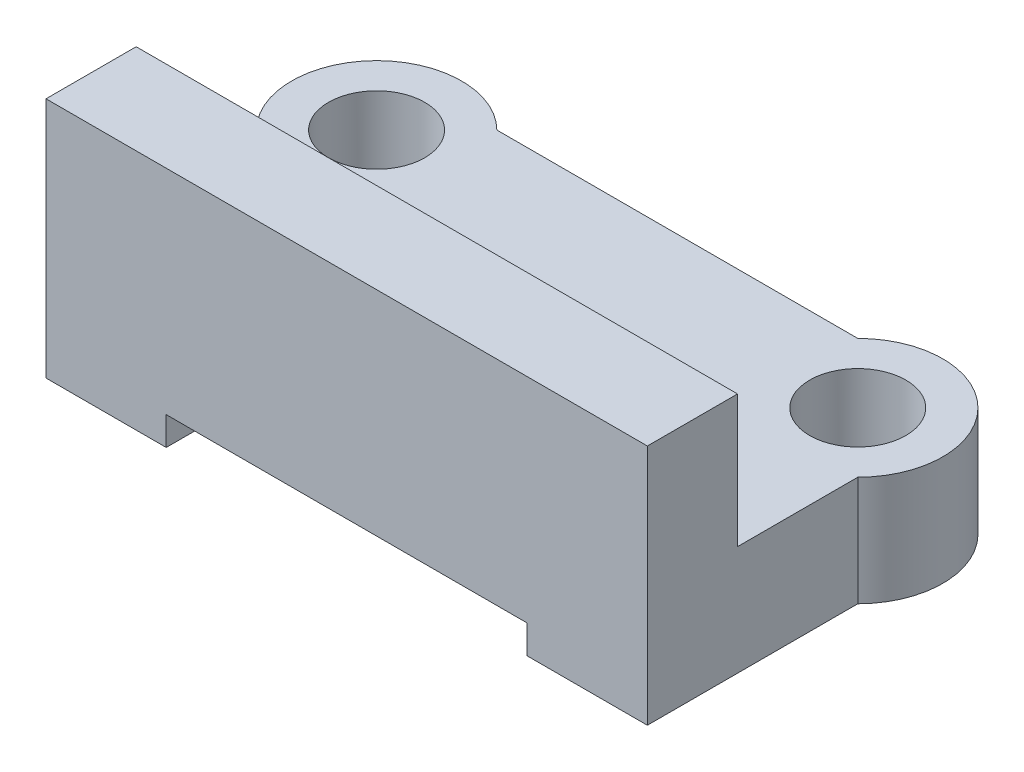
SolidWorks part; units mm, degrees
ref_plane "Front Plane" through (0, 0, 0) normal (0, 0, 1) x (1, 0, 0)
ref_plane "Top Plane" through (0, 0, 0) normal (0, 1, 0) x (1, 0, 0)
ref_plane "Right Plane" through (0, 0, 0) normal (1, 0, 0) x (0, 0, -1)
sketch "Sketch1" plane through (0, 0, 0) normal (0, 0, 1) x (1, 0, 0)
  line L0 (24.6185, -84.9027) -> (24.6185, -85.8498)
  line L1 (36.6261, -85.8498) -> (36.6261, -84.9027)
  line L2 (40.6261, -85.8498) -> (40.6261, -73.2027)
  line L3 (20.6185, -73.2027) -> (20.6185, -85.8498)
  line L6 (36.6261, -84.9027) -> (24.6185, -84.9027)
  line L8 (36.6261, -91.3148) -> (36.6261, -85.5592) construction
  line L10 (20.6185, -85.8498) -> (24.6185, -85.8498)
  line L11 (40.6261, -91.3148) -> (40.6261, -85.5592) construction
  line L14 (20.6185, -85.7535) -> (20.6185, -95.8462) construction
  line L15 (20.6185, -73.2027) -> (40.6261, -73.2027)
  line L16 (24.6185, -85.7535) -> (24.6185, -95.8462) construction
  line L18 (36.6261, -85.8498) -> (40.6261, -85.8498)
  dimension "D2" = 4
extrude "Boss-Extrude1" add sketch "Sketch1" along normal blind 3
sketch "Sketch2" plane through (0, 0, 0) normal (0, 0, -1) x (-1, 0, 0)
  line L0 (-40.6261, -73.2027) -> (-20.6185, -73.2027) construction
  line L1 (-40.6261, -73.2027) -> (-20.6185, -73.2027)
  line L2 (-40.6261, -73.2027) -> (-40.6261, -78.2027)
  line L3 (-40.6261, -78.2027) -> (-20.6185, -78.2027)
  line L4 (-20.6185, -73.2027) -> (-20.6185, -78.2027)
  line L5 (-20.6185, -73.2027) -> (-20.6185, -85.8498) construction
extrude "Boss-Extrude2" add sketch "Sketch2" along normal blind 8
sketch "Sketch3" plane through (0, 0, 0) normal (0, 0, -1) x (-1, 0, 0)
  line L8 (-20.6185, -78.2027) -> (-40.6261, -78.2027)
  line L9 (-40.6261, -78.2027) -> (-40.6261, -85.8498)
  line L10 (-40.6261, -85.8498) -> (-36.6261, -85.8498)
  line L11 (-36.6261, -85.8498) -> (-36.6261, -84.9027)
  line L12 (-36.6261, -84.9027) -> (-24.6185, -84.9027)
  line L13 (-24.6185, -84.9027) -> (-24.6185, -85.8498)
  line L14 (-24.6185, -85.8498) -> (-20.6185, -85.8498)
  line L15 (-20.6185, -85.8498) -> (-20.6185, -78.2027)
  line L17 (-40.6261, -82.2027) -> (-40.6261, -85.8498)
  line L18 (-40.6261, -85.8498) -> (-36.6261, -85.8498)
  line L19 (-36.6261, -85.8498) -> (-36.6261, -84.9027)
  line L20 (-36.6261, -84.9027) -> (-24.6185, -84.9027)
  line L21 (-24.6185, -84.9027) -> (-24.6185, -85.8498)
  line L22 (-24.6185, -85.8498) -> (-20.6185, -85.8498)
  line L23 (-20.6185, -85.8498) -> (-20.6185, -82.2027)
  line L24 (-40.6261, -82.2027) -> (-20.6185, -82.2027)
  dimension "D1" = 0
extrude "Boss-Extrude3" add sketch "Sketch3" along normal blind 8
sketch "Sketch4" plane through (0, 0, 3) normal (0, 0, 1) x (1, 0, 0)
  line L0 (40.6261, -73.2027) -> (20.6185, -73.2027) construction
  line L1 (24.6185, -73.2027) -> (36.6261, -73.2027)
  line L2 (24.6185, -73.2027) -> (24.6185, -74.6027)
  line L3 (24.6185, -74.6027) -> (36.6261, -74.6027)
  line L4 (36.6261, -73.2027) -> (36.6261, -74.6027)
  dimension "D1" = 1.4
extrude "Cut-Extrude1" cut sketch "Sketch4" against normal blind 27.7
hole_wizard "M3 Clearance Hole1" positions "Sketch6" profile "Sketch5" hole size "M3" standard "ISO"
sketch "Sketch6" plane through (0, -73.2027, 0) normal (0, 1, 0) x (1, 0, 0)
  line L0 (20.6185, -3) -> (20.6185, 8) construction
  line L1 (40.6261, -3) -> (40.6261, 8) construction
  line L2 (36.6261, 8) -> (40.6261, 8) construction
  line L3 (20.6185, 8) -> (24.6185, 8) construction
  point P0 (22.6185, 6)
  point P2 (38.6261, 6)
  dimension "D1" = 2
  dimension "D2" = 2
  dimension "D3" = 2
  dimension "D4" = 2
sketch "Sketch5" plane through (22.6185, -73.2027, -6) normal (1, 0, 0) x (0, 0, 1)
  line L0 (0, 0) -> (0, 16.4614)
  line L1 (0, 16.4614) -> (1.6, 15.5)
  line L2 (1.6, 15.5) -> (1.6, 0)
  line L5 (1.6, 0) -> (0, 0)
  line L10 (0, 16.4614) -> (-1.6, 15.5) construction
  line L11 (0, -6.35) -> (0, 107.95) construction
  dimension "Hole Dia." = 3.2
  dimension "Hole Depth" = 15.5
  dimension "Drill Angle" = 118
sketch "Sketch7" plane through (40.6261, 0, 0) normal (1, 0, 0) x (0, 0, -1)
  line L0 (8, -78.2027) -> (0, -78.2027) construction
  line L1 (0, -78.2027) -> (8, -78.2027)
  line L2 (0, -78.2027) -> (0, -77.8027)
  line L3 (0, -77.8027) -> (8, -77.8027)
  line L4 (8, -78.2027) -> (8, -77.8027)
  line L5 (8, -73.2027) -> (8, -78.2027) construction
  dimension "D1" = 0.4
extrude "Cut-Extrude2" cut sketch "Sketch7" against normal blind 28.5
sketch "Sketch8" plane through (0, -73.2027, 0) normal (0, 1, 0) x (1, 0, 0)
  line L0 (20.6185, 4) -> (20.6185, 8)
  line L1 (20.6185, -3) -> (20.6185, 8) construction
  line L2 (20.6185, 8) -> (24.6185, 8)
  line L3 (24.6185, 8) -> (24.6185, -3) construction
  line L4 (40.6261, 8) -> (36.6261, 8)
  line L5 (36.6261, 8) -> (40.6261, 8) construction
  line L8 (40.6261, 8) -> (40.6261, 4)
  line L9 (40.6261, -3) -> (40.6261, 8) construction
  arc A0 (40.6261, 4) -> (36.6261, 8) centre (38.6261, 6) ccw
  arc A1 (24.6185, 8) -> (20.6185, 4) centre (22.6185, 6) ccw
  line M2 (40.6261, 8) -> (36.6261, 8)
  line M5 (40.6261, -3) -> (40.6261, 8)
extrude "Boss-Extrude4" add sketch "Sketch8" against normal up to surface (4.6 mm away) contours L2 A1 | L0 A1 | A0 M2 | A0 M5 region at (20.2826, -73.2027, -6) region at (22.6185, -73.2027, -8.3359) region at (40.9621, -73.2027, -6) region at (38.6261, -73.2027, -8.3359) up to face at (22.6185, -77.8027, -4.4)
sketch "Sketch9" plane through (0, -85.8498, 0) normal (0, -1, 0) x (1, 0, 0)
  line L0 (20.6185, -4) -> (20.6185, -8)
  line L1 (20.6185, -8) -> (24.6185, -8)
  line L2 (36.6261, -8) -> (40.6261, -8)
  line L3 (40.6261, -8) -> (40.6261, -4)
  arc A0 (20.6185, -4) -> (24.6185, -8) centre (22.6185, -6) ccw construction
  arc A1 (20.6185, -4) -> (24.6185, -8) centre (22.6185, -6) ccw
  arc A2 (36.6261, -8) -> (40.6261, -4) centre (38.6261, -6) ccw construction
  arc A3 (36.6261, -8) -> (40.6261, -4) centre (38.6261, -6) ccw
  line M2 (20.6185, 3) -> (20.6185, -8)
  line M3 (20.6185, -8) -> (24.6185, -8)
extrude "Boss-Extrude5" add sketch "Sketch9" against normal up to surface (3.6471 mm away) contours A1 M2 | A1 M3 | L2 A3 | L3 A3 region at (22.6185, -85.8498, -8.3359) region at (20.2826, -85.8498, -6) region at (40.9621, -85.8498, -6) region at (38.6261, -85.8498, -8.3359) up to face at (22.6185, -82.2027, -7.6)
sketch "Sketch10" plane through (0, 0, 3) normal (0, 0, 1) x (1, 0, 0)
  line L1 (17.0109, -70.1968) -> (42.7707, -70.1968)
  line L2 (17.0109, -70.1968) -> (17.0109, -77.8027)
  line L3 (17.0109, -77.8027) -> (42.7707, -77.8027)
  line L4 (42.7707, -70.1968) -> (42.7707, -77.8027)
extrude "Cut-Extrude3" cut sketch "Sketch10" against normal blind 15
